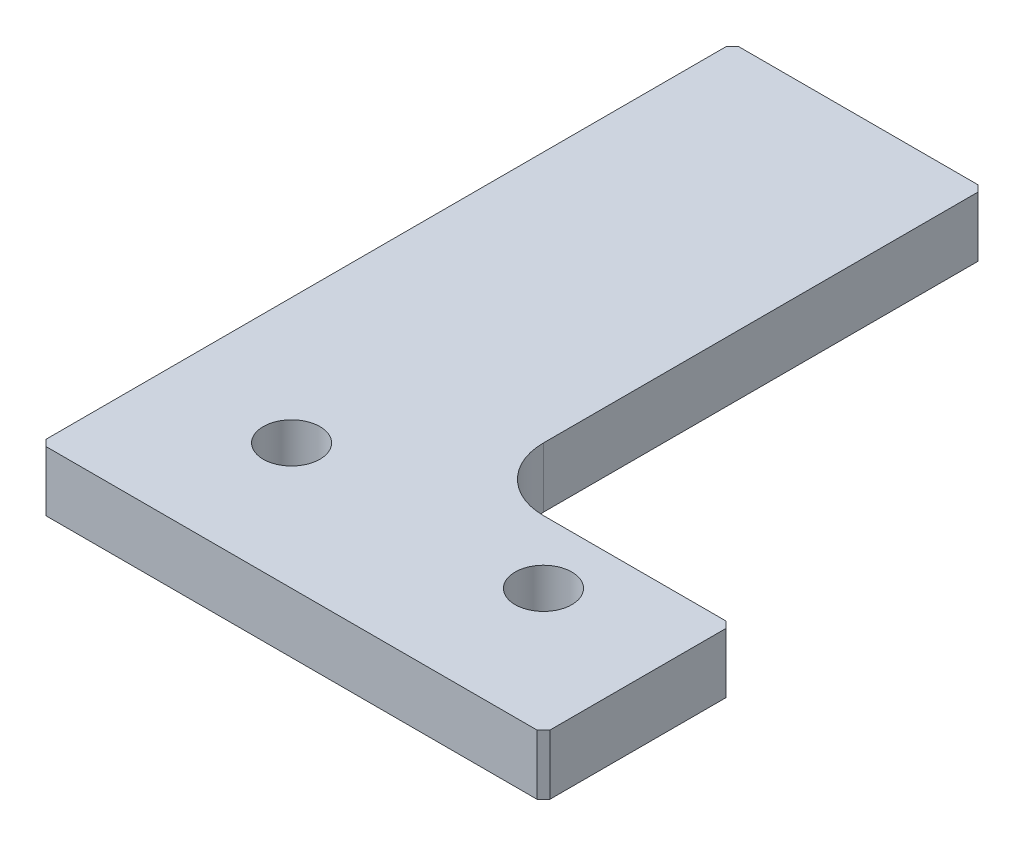
SolidWorks part; units mm, degrees
material "6061-T6 (SS)"
ref_plane "Front Plane" through (0, 0, 0) normal (0, 0, 1) x (1, 0, 0)
ref_plane "Top Plane" through (0, 0, 0) normal (0, 1, 0) x (1, 0, 0)
ref_plane "Right Plane" through (0, 0, 0) normal (1, 0, 0) x (0, 0, -1)
sketch "Sketch1" plane through (0, 0, 0) normal (0, 1, 0) x (1, 0, 0)
  line L0 (-20, 90) -> (-20, -20)
  line L1 (-20, -20) -> (60, -20)
  line L2 (60, -20) -> (60, 10)
  line L3 (60, 10) -> (20, 10)
  line L4 (20, 10) -> (20, 90)
  line L5 (20, 90) -> (-20, 90)
  line L6 (0, 0) -> (40, 0) construction
  dimension "D1" = 40
  dimension "D2" = 20
  dimension "D3" = 20
  dimension "D4" = 10
  dimension "D5" = 20
  dimension "D6" = 110
  dimension "D7" = 40
extrude "Boss-Extrude1" add sketch "Sketch1" along normal blind 9.525
hole_wizard "M8 Clearance Hole1" positions "Sketch2" profile "Sketch3" hole size "M8" standard "ANSI Metric" end condition up to next
sketch "Sketch2" plane through (0, 9.525, 0) normal (0, 1, 0) x (1, 0, 0)
  point P0 (0, 0)
  point P3 (40, 0)
sketch "Sketch3" plane through (0, 9.525, 0) normal (1, 0, 0) x (0, 0, 1)
  line L0 (0, 0) -> (0, 9.525)
  line L1 (0, 9.525) -> (4.5, 9.525)
  line L2 (4.5, 9.525) -> (4.5, 0)
  line L5 (4.5, 0) -> (0, 0)
  line L11 (0, -6.35) -> (0, 107.95) construction
  dimension "Thru Hole Dia." = 9
  dimension "Thru Hole Depth" = 9.525
fillet "Fillet1" radius 10 1 edges at (20, 4.7625, -10)
chamfer "Chamfer1" distance 1 5 edges at (60, 4.7625, -10) (60, 4.7625, 20) (-20, 4.7625, 20) (20, 4.7625, -90) (-20, 4.7625, -90)
